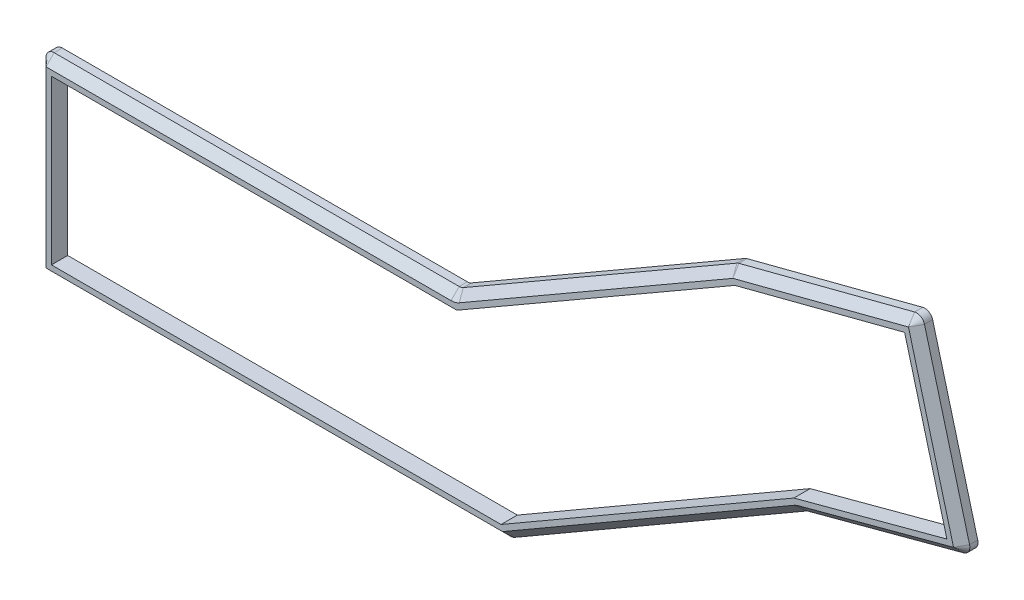
SolidWorks part; units mm, degrees
ref_plane "Plan de face" through (0, 0, 0) normal (0, 0, 1) x (1, 0, 0)
ref_plane "Plan de dessus" through (0, 0, 0) normal (0, 1, 0) x (1, 0, 0)
ref_plane "Plan de droite" through (0, 0, 0) normal (1, 0, 0) x (0, 0, -1)
sketch "Esquisse1" plane through (0, 0, 0) normal (0, 0, 1) x (1, 0, 0)
  line L0 (152.8114, 25.9717) -> (138.2826, 80.2215) construction
  line L1 (98.1506, 11.3316) -> (152.8114, 25.9717) construction
  line L2 (-9.3986, -50.8585) -> (98.1506, 11.3316) construction
  line L3 (-172.3739, -50.8585) -> (-9.3986, -50.8585) construction
  line L4 (-24.5886, 5.3017) -> (-172.3739, 5.2915) construction
  line L5 (138.2826, 80.2215) -> (78.0109, 64.5416) construction
  line L6 (-151.6088, 5.3124) -> (-151.6088, 5.2929)
  line L7 (-24.5886, 5.3017) -> (78.0109, 64.5416) construction
  line L8 (-172.3739, 5.2915) -> (-172.3739, -50.6876) construction
  line L9 (-172.3739, -50.6876) -> (-172.3739, -50.8585) construction
  line L10 (-25.1245, 7.3016) -> (-174.3739, 7.2914)
  line L11 (-174.3739, 7.2914) -> (-174.3739, -50.6876)
  line L12 (-174.3739, -50.6876) -> (-174.3739, -52.8585)
  line L13 (-174.3739, -52.8585) -> (-8.862, -52.8585)
  line L14 (-8.862, -52.8585) -> (98.9231, 9.4681)
  line L15 (98.9231, 9.4681) -> (155.2607, 24.5572)
  line L16 (155.2607, 24.5572) -> (139.7008, 82.657)
  line L17 (139.7008, 82.657) -> (77.2454, 66.409)
  line L18 (-25.1245, 7.3016) -> (77.2454, 66.409)
  line L19 (-26.4645, 12.3015) -> (-179.3739, 12.291)
  line L20 (-179.3739, 12.291) -> (-179.3739, -50.6876)
  line L21 (-179.3739, -50.6876) -> (-179.3739, -57.8585)
  line L22 (-179.3739, -57.8585) -> (-7.5204, -57.8585)
  line L23 (-7.5204, -57.8585) -> (100.8545, 4.8091)
  line L24 (100.8545, 4.8091) -> (161.3839, 21.021)
  line L25 (161.3839, 21.021) -> (143.2464, 88.7459)
  line L26 (143.2464, 88.7459) -> (75.3314, 71.0775)
  line L27 (-26.4645, 12.3015) -> (75.3314, 71.0775)
  circle A0 centre (80.6856, 58.4893) radius 1
  circle A1 centre (92.8776, 28.0855) radius 1
  circle A2 centre (-29.7028, -2.6485) radius 1
  circle A3 centre (-10.6528, -46.4381) radius 1
  circle A4 centre (-114.2594, -13.4181) radius 1
  circle A5 centre (-114.0308, -32.4935) radius 1
  dimension "D1" = 2
  dimension "D2" = 5
extrude "Boss.-Extru.1" add sketch "Esquisse1" along normal blind 6 contours L27 L19 L20 L21 L22 L23 L24 L25 L26 L10 L18 L17 L16 L15 L14 L13 L12 L11 region at (26.2883, 38.477, 0)
fillet "Congé1" radius 3 8 edges at (-179.3739, -57.8585, 3) (-7.5204, -57.8585, 3) (100.8545, 4.8091, 3) (161.3839, 21.021, 3) (143.2464, 88.7459, 3) (75.3314, 71.0775, 3) (-26.4645, 12.3015, 3) (-179.3739, 12.291, 3)
sketch "Esquisse2" plane through (0, 0, 0) normal (0, 0, 1) x (1, 0, 0)
  circle A0 centre (158.2016, 22.9581) radius 1
  circle A1 centre (141.3885, 85.5343) radius 1
  circle A2 centre (76.5002, 68.7766) radius 1
  circle A3 centre (99.8904, 7.0714) radius 1
  circle A4 centre (-8.1724, -55.2759) radius 1
  circle A5 centre (-25.6914, 9.9201) radius 1
  circle A6 centre (-176.5621, 9.9201) radius 1
  circle A7 centre (-177.0296, -55.2759) radius 1
extrude "Enlèv. mat.-Extru.1" cut sketch "Esquisse2" along normal blind 3
chamfer "Chanfrein1" distance 3 angle 45 16 edges at (-178.4953, 11.4125, 6) (-101.8212, 12.2964, 6) (-26.4919, 12.4038, 6) (24.6056, 41.7889, 6) (75.3418, 71.0522, 6) (108.0441, 79.5878, 6) (142.6286, 87.6851, 6) (152.3124, 54.8937, 6) (160.3079, 21.6424, 6) (129.8616, 12.5782, 6) (100.8645, 4.785, 6) (46.844, -26.4224, 6) (-7.5479, -57.756, 6) (-92.3496, -57.8585, 6) (-178.4952, -56.9798, 6) (-179.3739, -22.7836, 6)
